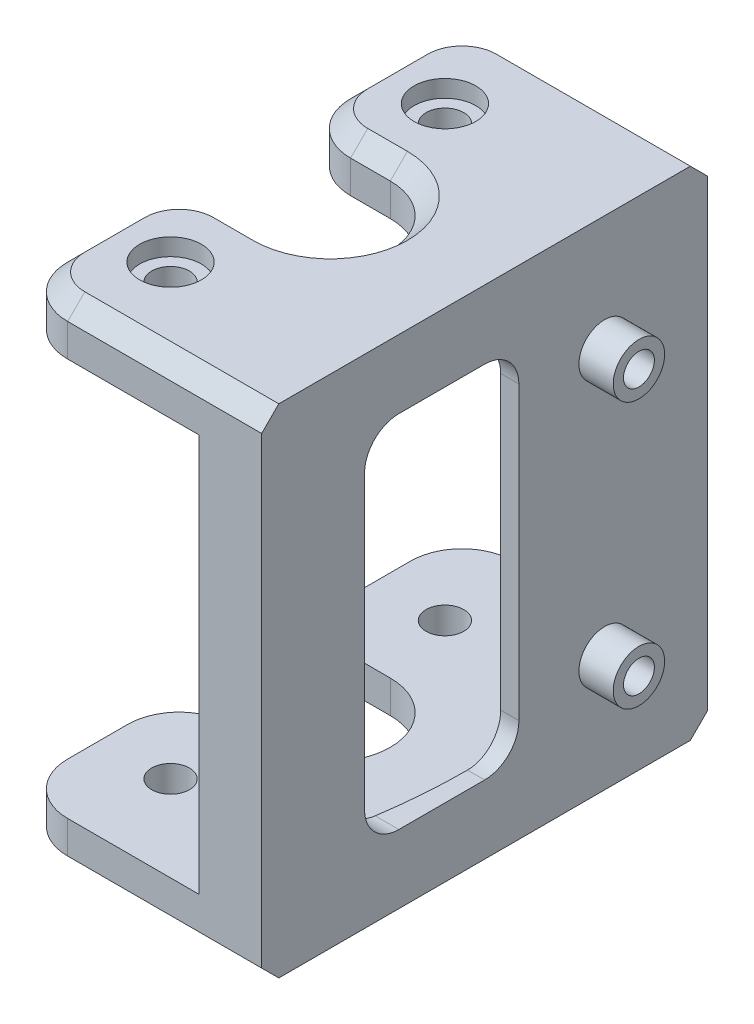
SolidWorks part; units mm, degrees
ref_plane "Спереди" through (0, 0, 0) normal (0, 0, 1) x (1, 0, 0)
ref_plane "Сверху" through (0, 0, 0) normal (0, 1, 0) x (1, 0, 0)
ref_plane "Справа" through (0, 0, 0) normal (1, 0, 0) x (0, 0, -1)
sketch "Эскиз1" plane through (0, 0, 0) normal (0, 1, 0) x (1, 0, 0)
  line L0 (23.6854, 8) -> (23.6854, -8) construction
  line L1 (19.6854, 13) -> (34, 13)
  line L2 (19.6854, 13) -> (19.6854, -13)
  line L3 (19.6854, -13) -> (34, -13)
  line L4 (34, 13) -> (34, -13)
  line L5 (19.6854, 13) -> (34, -13) construction
  line L6 (19.6854, -13) -> (34, 13) construction
  line L7 (25, 3.5) -> (19.6854, 3.5)
  line L8 (25, -3.5) -> (19.6854, -3.5)
  circle A0 centre (0, 0) radius 25 construction
  circle A1 centre (23.6854, 8) radius 1.1
  circle A2 centre (23.6854, -8) radius 1.1
  circle A3 centre (25, 0) radius 3.5
  point P3 (26.8427, 0)
  dimension "D1" = 50
  dimension "D2" = 2.2
  dimension "D3" = 2.2
  dimension "D8" = 7
  dimension "D4" = 16
  dimension "D5" = 4
  dimension "D6" = 34
  dimension "D7" = 26
extrude "Бобышка-Вытянуть1" add sketch "Эскиз1" along normal mid plane 29 contours A3 L8 L2 L3 L4 L1 L7 A2 A1 region at (26.8427, 0, -12.7032)
sketch "Эскиз2" plane through (0, 0, 0) normal (0, 1, 0) x (1, 0, 0)
  circle A0 centre (0, 0) radius 33
  dimension "D1" = 66
extrude "Вырез-Вытянуть1" cut sketch "Эскиз2" against normal mid plane 23.2 contours A0
sketch "Эскиз3" plane through (34, 0, 0) normal (1, 0, 0) x (0, 0, -1)
  line L0 (-13, 0) -> (13, 0) construction
  line L5 (-7, 10.5) -> (2, 10.5)
  line L6 (-7, 10.5) -> (-7, -10.5)
  line L7 (-7, -10.5) -> (2, -10.5)
  line L8 (2, 10.5) -> (2, -10.5)
  line L9 (-7, 10.5) -> (2, -10.5) construction
  line L10 (-7, -10.5) -> (2, 10.5) construction
  line L11 (-13, 14.5) -> (-13, -14.5) construction
  line L12 (13, 14.5) -> (13, -14.5) construction
  circle A0 centre (7, 7.75) radius 0.9
  circle A1 centre (7, -7.75) radius 0.9
  point P0 (-2.5, 0)
  dimension "D5" = 1.8
  dimension "D1" = 6
  dimension "D2" = 5
  dimension "D3" = 21
  dimension "D4" = 6
  dimension "D6" = 15.5
extrude "Вырез-Вытянуть2" cut sketch "Эскиз3" against normal through all
sketch "Эскиз4" plane through (34, 0, 0) normal (1, 0, 0) x (0, 0, -1)
  circle A0 centre (7, 7.75) radius 1.5
  circle A1 centre (7, -7.75) radius 1.5
  circle A11 centre (7, 7.75) radius 0.9
  circle A12 centre (7, 7.75) radius 0.9
  circle A14 centre (7, -7.75) radius 0.9
  circle A15 centre (7, -7.75) radius 0.9
  dimension "D1" = 3
  dimension "D2" = 3
extrude "Бобышка-Вытянуть2" add sketch "Эскиз4" along normal blind 2
fillet "Скругление1" radius 2 4 edges at (33.4697, -10.5, -2) (33.4697, 10.5, -2) (33.1245, 10.5, 7) (33.1245, -10.5, 7)
fillet "Скругление2" radius 3 8 edges at (19.6854, -13.05, -13) (19.6854, -13.05, -3.5) (19.6854, -13.05, 3.5) (19.6854, -13.05, 13) (19.6854, 13.05, -13) (19.6854, 13.05, -3.5) (19.6854, 13.05, 3.5) (19.6854, 13.05, 13)
chamfer "Фаска1" distance 1 angle 45 22 edges at (28.3427, -14.5, -13) (20.5641, -14.5, -12.1213) (19.6854, -14.5, -8.25) (20.5641, -14.5, -4.3787) (23.8427, -14.5, -3.5) (28.5, -14.5, 0) (23.8427, -14.5, 3.5) (20.5641, -14.5, 4.3787) (19.6854, -14.5, 8.25) (20.5641, -14.5, 12.1213) (28.3427, -14.5, 13) (28.3427, 14.5, -13) (20.5641, 14.5, -12.1213) (19.6854, 14.5, -8.25) (20.5641, 14.5, -4.3787) (23.8427, 14.5, -3.5) (28.5, 14.5, 0) (23.8427, 14.5, 3.5) (20.5641, 14.5, 4.3787) (19.6854, 14.5, 8.25) (20.5641, 14.5, 12.1213) (28.3427, 14.5, 13)
sketch "Эскиз5" plane through (0, 14.5, 0) normal (0, 1, 0) x (1, 0, 0)
  circle A0 centre (23.6854, -8) radius 1.8
  circle A1 centre (23.6854, 8) radius 1.8
  dimension "D1" = 3.6
  dimension "D2" = 3.6
extrude "Вырез-Вытянуть3" cut sketch "Эскиз5" against normal blind 1
mirror "Зеркальное отражение1" about plane through (0, 0, 0) normal (0, 1, 0) of "Вырез-Вытянуть3"
equation "\"motor_diameter\"= 30"
equation "\"mm_diameter\"= IIF ( \"motor_diameter\" < 34 , 41 , \"motor_diameter\" + 8 )"
equation "\"upper_shafts_diameter\"= 5"
equation "\"upper_shats_length\"= 180"
equation "\"upper_bearing_d1\"= 10"
equation "\"upper_bearing_d2\"= 5"
equation "\"upper_bearing_h\"= 15"
equation "\"lower_shafts_diameter\"= 5"
equation "\"lower_shafts_length\"= 180"
equation "\"lower_bearing_d1\"= 10"
equation "\"lower_bearing_d2\"= 5"
equation "\"lower_bearing_h\"= 15"
equation "\"print_offset\"= 0.2"
equation "\"bh_screws_d\"= 2"
equation "\"bh_screws_h\"= 20"
equation "\"bh_screws_hh_d\"= 3.4"
equation "\"bh_screws_hh_h\"= 2"
equation "\"bh_nut_d\"= 3.8"
equation "\"bh_nut_h\"= 2"
equation "\"motor_screws_d\"= 3"
equation "\"motor_screws_h\"= 16"
equation "\"motor_screws_hh_d\"= 5.5"
equation "\"motor_screws_hh_h\"= 3"
equation "\"plate_hole_distance\"= 25.4"
equation "\"plate_screws_d\"= 6.5"
equation "\"shafts_diameter\"= IIF ( \"mm_diameter\" < 42 , 42 + 8 , \"mm_diameter\" + 8 )"
equation "\"central_hole_diameter\"= 8"
equation "\"bh_thikness\"= 4"
equation "\"ends_screws_d\"= 4"
equation "\"ends_screws_h\"= 16"
equation "\"ends_screws_hh_d\"= 6.7"
equation "\"ends_screws_hh_h\"= 4.1"
equation "\"ends_nut_d\"= 6.8"
equation "\"ends_nut_h\"= 3"
equation "\"system_radius\" = ( \"shafts_diameter\" + 12 + \"bh_thikness\" / 2 ) / 2"
equation "\"encoder_distance\"= \"system_radius\" + 4"
equation "\"tape_position\"= \"encoder_distance\" - 2 + 3.9 + 1.7 / 2"
equation "\"D1@Эскиз1\"=\"shafts_diameter\""
equation "\"D2@Эскиз1\"=\"bh_screws_d\"+\"print_offset\""
equation "\"D3@Эскиз1\"=\"D2@Эскиз1\""
equation "\"D5@Эскиз1\"=\"bh_thikness\""
equation "\"D6@Эскиз1\"=\"encoder_distance\"-2"
equation "\"D8@Эскиз1\"=\"lower_shafts_diameter\"+2"
equation "\"D1@Бобышка-Вытянуть1\"=\"lower_bearing_h\"+\"bh_thikness\"*2+6"
equation "\"D1@Эскиз2\"=\"system_radius\"*2+2"
equation "\"D1@Вырез-Вытянуть1\"=\"lower_bearing_h\"+\"print_offset\"+\"bh_thikness\"*2"
equation "\"D5@Эскиз3\"=\"bh_screws_d\"-\"print_offset\""
equation "\"D2@Эскиз4\"=\"D1@Эскиз4\""
equation "\"D1@Эскиз5\"=\"bh_screws_hh_d\"+\"print_offset\""
equation "\"D2@Эскиз5\"=\"D1@Эскиз5\""
